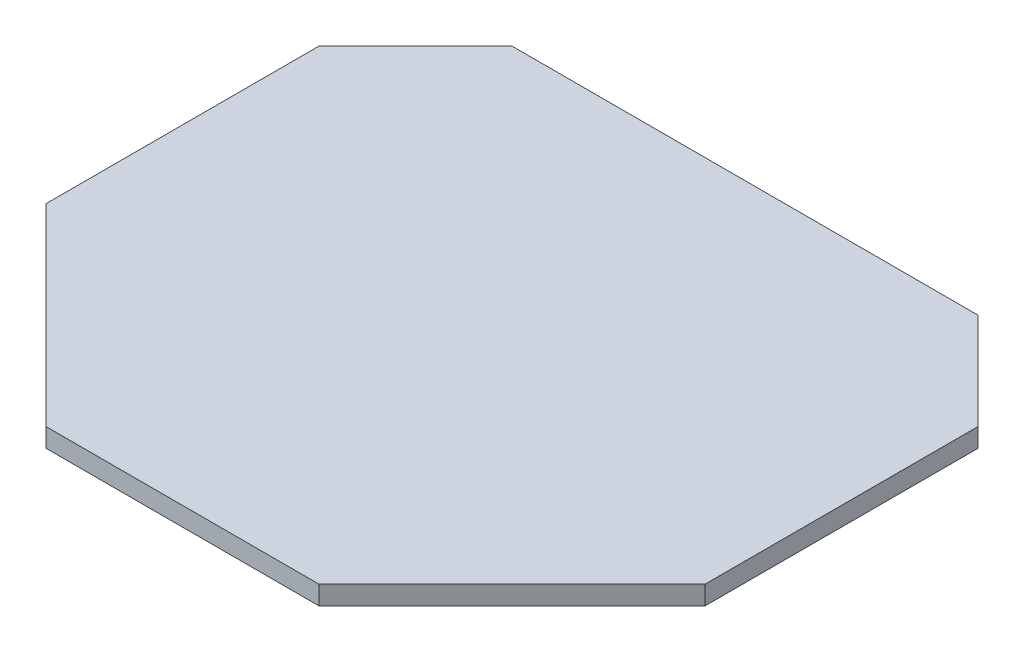
SolidWorks part; units mm, degrees
ref_plane "Front Plane" through (0, 0, 0) normal (0, 0, 1) x (1, 0, 0)
ref_plane "Top Plane" through (0, 0, 0) normal (0, 1, 0) x (1, 0, 0)
ref_plane "Right Plane" through (0, 0, 0) normal (1, 0, 0) x (0, 0, -1)
sketch "Sketch1" plane through (0, 0, 0) normal (0, 1, 0) x (1, 0, 0)
  line L0 (0, 0) -> (53.993, 22.3647) construction
  line L1 (0, 0) -> (108.3865, 0) construction
  line L2 (35, 14.4975) -> (14.4975, 35) construction
  line L3 (14.4975, 35) -> (-14.4975, 35) construction
  line L4 (-14.4975, 35) -> (-35, 14.4975) construction
  line L5 (-35, 14.4975) -> (-35, -14.4975) construction
  line L6 (-35, -14.4975) -> (-14.4975, -35) construction
  line L7 (-14.4975, -35) -> (14.4975, -35) construction
  line L8 (14.4975, -35) -> (35, -14.4975) construction
  line L9 (35, -14.4975) -> (35, 14.4975) construction
  line L10 (-35, -14.4975) -> (-14.4975, -35)
  line L11 (-14.4975, -35) -> (14.4975, -35)
  line L12 (14.4975, -35) -> (35, -14.4975)
  line L13 (35, -14.4975) -> (35, 14.4975)
  line L14 (35, 14.4975) -> (24.7487, 24.7487)
  line L15 (24.7487, 24.7487) -> (-24.7487, 24.7487)
  line L16 (-24.7487, 24.7487) -> (-35, 14.4975)
  line L17 (-35, 14.4975) -> (-35, -14.4975)
  circle A0 centre (0, 0) radius 35 construction
  dimension "D1" = 35
extrude "Boss-Extrude1" add sketch "Sketch1" along normal blind 2
